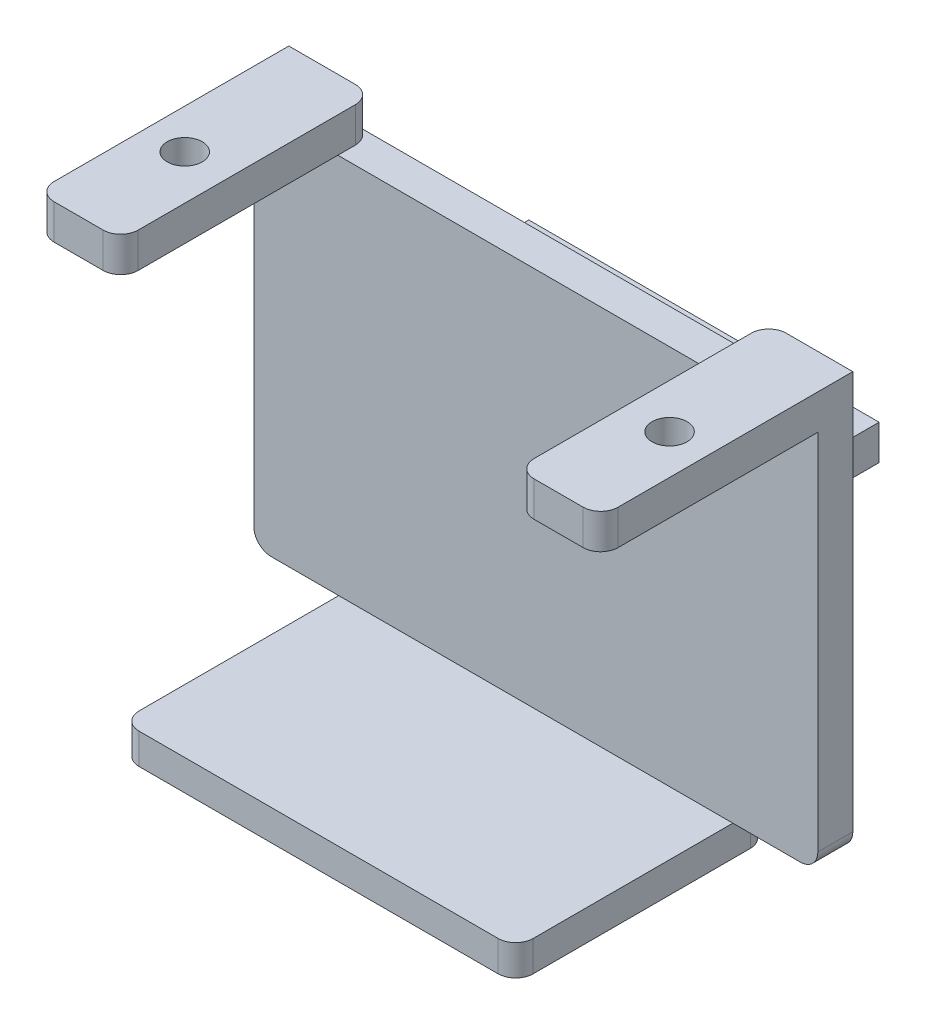
SolidWorks part; units mm, degrees
ref_plane "Front Plane" through (0, 0, 0) normal (0, 0, 1) x (1, 0, 0)
ref_plane "Top Plane" through (0, 0, 0) normal (0, 1, 0) x (1, 0, 0)
ref_plane "Right Plane" through (0, 0, 0) normal (1, 0, 0) x (0, 0, -1)
sketch "Sketch1" plane through (0, 0, 0) normal (0, 0, 1) x (1, 0, 0)
  line L1 (-16.1, 12.75) -> (16.1, 12.75)
  line L2 (-16.1, 12.75) -> (-16.1, -12.75)
  line L3 (-16.1, -12.75) -> (16.1, -12.75)
  line L4 (16.1, 12.75) -> (16.1, -12.75)
  line L5 (-16.1, 12.75) -> (16.1, -12.75) construction
  line L6 (-16.1, -12.75) -> (16.1, 12.75) construction
  point P0 (0, 0)
  dimension "D1" = 32.2
  dimension "D2" = 25.5
extrude "Boss-Extrude1" add sketch "Sketch1" along normal blind 14.4
sketch "Sketch3" plane through (0, 0, 14.4) normal (0, 0, 1) x (1, 0, 0)
  line L0 (-16.1, 12.75) -> (-16.1, -12.75) construction
  line L1 (-16.1, 10.75) -> (16.1, 10.75)
  line L2 (-16.1, 10.75) -> (-16.1, -11)
  line L3 (-16.1, -11) -> (16.1, -11)
  line L4 (16.1, 10.75) -> (16.1, -11)
  line L5 (16.1, -12.75) -> (16.1, 12.75) construction
  line L6 (16.1, 12.75) -> (-16.1, 12.75) construction
  dimension "D1" = 2
  dimension "D2" = 21.75
extrude "Cut-Extrude1" cut sketch "Sketch3" against normal blind 12.4
sketch "Sketch5" plane through (0, 0, 14.4) normal (0, 0, 1) x (1, 0, 0)
  line L0 (16.1, 12.75) -> (-16.1, 12.75) construction
  line L1 (-11.3, 12.75) -> (11.3, 12.75)
  line L2 (-11.3, 12.75) -> (-11.3, 10.75)
  line L3 (-11.3, 10.75) -> (11.3, 10.75)
  line L4 (11.3, 12.75) -> (11.3, 10.75)
  line L5 (16.1, 10.75) -> (-16.1, 10.75) construction
  line L6 (-16.1, 12.75) -> (-16.1, 10.75) construction
  line L7 (16.1, 10.75) -> (16.1, 12.75) construction
  dimension "D1" = 4.8
  dimension "D2" = 4.8
extrude "Cut-Extrude2" cut sketch "Sketch5" against normal blind 14.4 contours L2 L1 L4 L3
fillet "Fillet1" radius 1 1 edges at (-11.3, 11.75, 14.4)
fillet "Fillet2" radius 1 1 edges at (-16.1, 11.75, 14.4)
fillet "Fillet3" radius 1 1 edges at (11.3, 11.75, 14.4)
fillet "Fillet4" radius 1 1 edges at (16.1, 11.75, 14.4)
sketch "Sketch10" plane through (0, 12.75, 0) normal (0, 1, 0) x (1, 0, 0)
  line L0 (-16.1, -13.4) -> (-16.1, 0) construction
  circle A0 centre (-13.84, -8.203) radius 1
  dimension "D1" = 2.26
extrude "Cut-Extrude3" cut sketch "Sketch10" against normal blind 10
mirror "Mirror1" about plane through (0, 0, 0) normal (1, 0, 0) of "Cut-Extrude3"
sketch "Sketch11" plane through (0, 0, 14.4) normal (0, 0, 1) x (1, 0, 0)
  line L0 (-16.1, -12.75) -> (16.1, -12.75) construction
  line L1 (-16.1, -11) -> (-11.25, -11)
  line L2 (-16.1, -11) -> (-16.1, -12.75)
  line L3 (-16.1, -12.75) -> (-11.25, -12.75)
  line L4 (-11.25, -11) -> (-11.25, -12.75)
  dimension "D1" = 4.85
extrude "Cut-Extrude4" cut sketch "Sketch11" against normal blind 20
mirror "Mirror2" about plane through (0, 0, 0) normal (1, 0, 0) of "Cut-Extrude4"
fillet "Fillet5" radius 1 6 edges at (-11.25, -11.875, 0) (-16.1, -11, 1) (16.1, -11, 1) (11.25, -11.875, 0) (11.25, -11.875, 14.4) (-11.25, -11.875, 14.4)
fillet "Fillet6" radius 1 2 edges at (-11.3, 11.75, 0) (11.3, 11.75, 0)
sketch "Sketch12" plane through (0, 0, 0) normal (0, 0, -1) x (-1, 0, 0)
  line L1 (-12.6, 6) -> (7.4, 6)
  line L2 (-12.6, 6) -> (-12.6, 4)
  line L3 (-12.6, 4) -> (7.4, 4)
  line L4 (7.4, 6) -> (7.4, 4)
  line L6 (12.3, 10.75) -> (-12.3, 10.75) construction
  line L9 (-16.1, -10) -> (-16.1, 12.75) construction
  dimension "D1" = 4.75
  dimension "D2" = 2
  dimension "D3" = 20
  dimension "D4" = 3.5
extrude "Boss-Extrude2" add sketch "Sketch12" along normal blind 5
